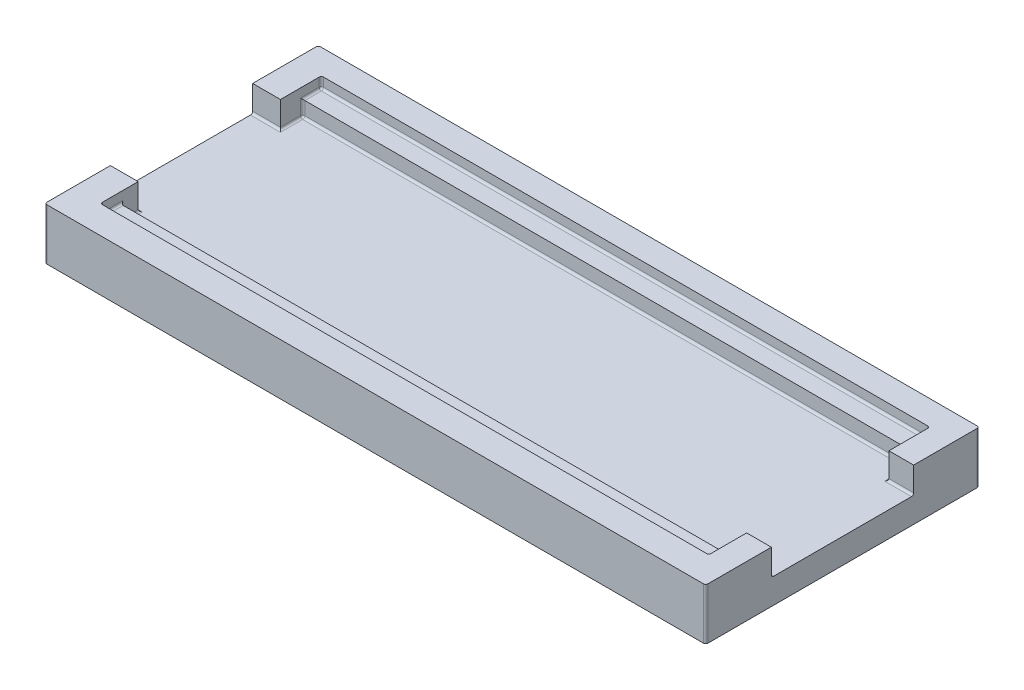
SolidWorks part; units mm, degrees
ref_plane "Front Plane" through (0, 0, 0) normal (0, 0, 1) x (1, 0, 0)
ref_plane "Top Plane" through (0, 0, 0) normal (0, 1, 0) x (1, 0, 0)
ref_plane "Right Plane" through (0, 0, 0) normal (1, 0, 0) x (0, 0, -1)
sketch "Sketch1" plane through (0, 0, 0) normal (0, 1, 0) x (1, 0, 0)
  line L1 (0, 0) -> (302, 0)
  line L2 (0, 0) -> (0, 125)
  line L3 (0, 125) -> (302, 125)
  line L4 (302, 0) -> (302, 125)
  dimension "D1" = 125
  dimension "D2" = 302
extrude "Boss-Extrude1" add sketch "Sketch1" along normal blind 23.5
sketch "Sketch2" plane through (0, 23.5, 0) normal (0, 1, 0) x (1, 0, 0)
  line L0 (0, 125) -> (0, 0) construction
  line L1 (12.7, 113.7) -> (290.7, 113.7)
  line L2 (12.7, 113.7) -> (12.7, 12.7)
  line L3 (12.7, 12.7) -> (290.7, 12.7)
  line L4 (290.7, 113.7) -> (290.7, 12.7)
  line L5 (0, 0) -> (302, 0) construction
  dimension "D1" = 12.7
  dimension "D2" = 12.7
  dimension "D3" = 101
  dimension "D4" = 278
extrude "Cut-Extrude1" cut sketch "Sketch2" against normal blind 5
sketch "Sketch3" plane through (0, 18.5, 0) normal (0, 1, 0) x (1, 0, 0)
  line L0 (290.7, 12.7) -> (290.7, 113.7) construction
  line L1 (290.7, 105.15) -> (12.7, 105.15)
  line L2 (290.7, 105.15) -> (290.7, 22.15)
  line L3 (290.7, 22.15) -> (12.7, 22.15)
  line L4 (12.7, 105.15) -> (12.7, 22.15)
  line L5 (290.7, 113.7) -> (12.7, 113.7) construction
  dimension "D1" = 278
  dimension "D2" = 83
  dimension "D3" = 8.55
extrude "Cut-Extrude2" cut sketch "Sketch3" against normal blind 7
fillet "Fillet2" radius 1 6 edges at (12.7, 21, -12.7) (290.7, 21, -12.7) (290.7, 15, -22.15) (290.7, 18.5, -17.425) (12.7, 18.5, -17.425) (12.7, 15, -22.15)
fillet "Fillet3" radius 1 10 edges at (12.9929, 18.7929, -12.9929) (290.4071, 18.7929, -12.9929) (12.7, 21, -113.7) (12.7, 18.5, -109.425) (12.7, 15, -105.15) (151.7, 18.5, -12.7) (151.7, 18.5, -113.7) (290.7, 15, -105.15) (290.7, 18.5, -109.425) (290.7, 21, -113.7)
fillet "Fillet4" radius 1 1 edges at (0, 11.75, -125)
fillet "Fillet5" radius 1 1 edges at (302, 11.75, -125)
fillet "Fillet6" radius 1 1 edges at (0, 11.75, 0)
fillet "Fillet7" radius 1 1 edges at (302, 11.75, 0)
sketch "Sketch4" plane through (0, 23.5, 0) normal (0, 1, 0) x (1, 0, 0)
  line L0 (0, 124) -> (0, 1) construction
  line L1 (0, 30) -> (12.7, 30)
  line L2 (0, 30) -> (0, 95)
  line L3 (0, 95) -> (12.7, 95)
  line L4 (12.7, 30) -> (12.7, 95)
  line L5 (12.7, 112.7) -> (12.7, 13.7) construction
  line L6 (1, 0) -> (301, 0) construction
  line L7 (301, 125) -> (1, 125) construction
  dimension "D1" = 30
  dimension "D2" = 30
extrude "Cut-Extrude3" cut sketch "Sketch4" against normal blind 12
sketch "Sketch5" plane through (0, 23.5, 0) normal (0, 1, 0) x (1, 0, 0)
  line L0 (302, 1) -> (302, 124) construction
  line L1 (302, 95) -> (290.7, 95)
  line L2 (302, 95) -> (302, 30)
  line L3 (302, 30) -> (290.7, 30)
  line L4 (290.7, 95) -> (290.7, 30)
  line L5 (290.7, 13.7) -> (290.7, 112.7) construction
  line L6 (1, 0) -> (301, 0) construction
  line L7 (301, 125) -> (1, 125) construction
  dimension "D1" = 30
  dimension "D2" = 30
extrude "Cut-Extrude4" cut sketch "Sketch5" against normal blind 12
fillet "Fillet9" radius 1 14 edges at (290.4071, 11.5, -104.8571) (12.9929, 11.5, -104.8571) (12.9929, 11.5, -22.4429) (290.4071, 11.5, -22.4429) (296.35, 11.5, -95) (290.7, 11.5, -99.575) (151.7, 11.5, -105.15) (12.7, 11.5, -99.575) (6.35, 11.5, -95) (6.35, 11.5, -30) (12.7, 11.5, -26.575) (290.7, 11.5, -26.575) (151.7, 11.5, -22.15) (296.35, 11.5, -30)
